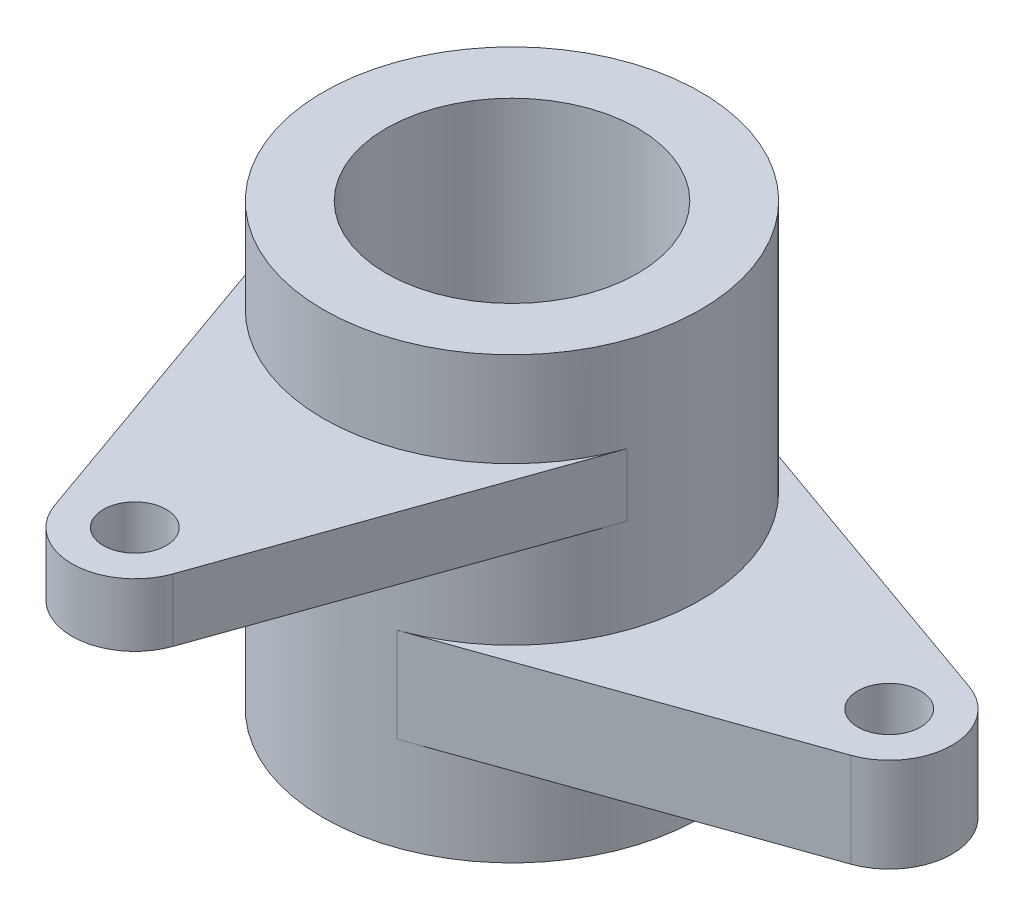
SolidWorks part; units mm, degrees
ref_plane "Front Plane" through (0, 0, 0) normal (0, 0, 1) x (1, 0, 0)
ref_plane "Top Plane" through (0, 0, 0) normal (0, 1, 0) x (1, 0, 0)
ref_plane "Right Plane" through (0, 0, 0) normal (1, 0, 0) x (0, 0, -1)
sketch "Sketch1" plane through (0, 0, 0) normal (0, 1, 0) x (1, 0, 0)
  circle A0 centre (0, 0) radius 30
  circle A1 centre (0, 0) radius 20
  dimension "D1" = 40
  dimension "D2" = 60
extrude "Boss-Extrude1" add sketch "Sketch1" against normal blind 70
sketch "Sketch2" plane through (0, 0, 0) normal (0, 1, 0) x (1, 0, 0)
  line L0 (0, 0) -> (0, 64.8452) construction
  line L1 (0, 0) -> (0, -60) construction
  line L2 (-28.2843, -10) -> (-9.4281, -63.3333)
  line L3 (9.4281, -63.3333) -> (28.2843, -10)
  circle A0 centre (0, 0) radius 30 construction
  arc A1 (-9.4281, -63.3333) -> (9.4281, -63.3333) centre (0, -60) ccw
  circle A2 centre (0, -60) radius 5
  arc A3 (-28.2843, -10) -> (0, 30) centre (0, 0) ccw
  circle M5 centre (0, 0) radius 30
  dimension "D2" = 10
  dimension "D3" = 10
  dimension "D1" = 60
extrude "Boss-Extrude2" add sketch "Sketch2" against normal blind 10 from offset 15 contours L2 A1 L3 A2 M5 region at (0, 0, 42.5792) offset against normal yes
extrude "Boss-Extrude3" add sketch "Sketch2<3>" against normal blind 15 from offset 40 separate body contours L2 A1 L3 A2 M5 region at (0, 0, 42.5792) offset against normal yes
sketch "Sketch2<3>" plane through (0, 0, 0) normal (0, 1, 0) x (1, 0, 0) same geometry as "Sketch2"
ref_axis "Axis1" through (0, -70, 0) along (0, 1, 0)
move or copy body "Body-Move/Copy1" bodies to move or copy 103 copy no rotation origin (0, 0, 0) rotation axis (0, 1, 0) rotation angle 90
